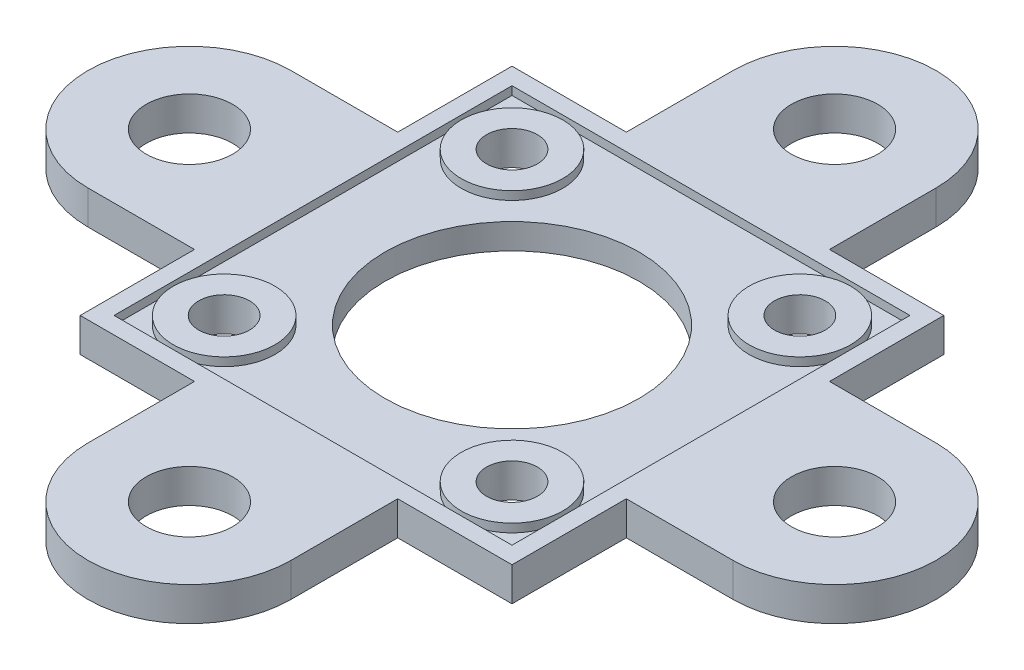
SolidWorks part; units mm, degrees
ref_plane "Front Plane" through (0, 0, 0) normal (0, 0, 1) x (1, 0, 0)
ref_plane "Top Plane" through (0, 0, 0) normal (0, 1, 0) x (1, 0, 0)
ref_plane "Right Plane" through (0, 0, 0) normal (1, 0, 0) x (0, 0, -1)
other "Bounding Box"
ref_plane "Default Plane" through (-8.9266, -12.7485, 0) normal (-0.1736, 0.9848, 0) x (0.9848, 0.1736, 0)
sketch "Sketch1" plane through (0, 0, 0) normal (0, 1, 0) x (1, 0, 0)
  line L1 (-11.5, -11.5) -> (11.5, -11.5)
  line L2 (-11.5, -11.5) -> (-11.5, 11.5)
  line L3 (-11.5, 11.5) -> (11.5, 11.5)
  line L4 (11.5, -11.5) -> (11.5, 11.5)
  line L5 (-11.5, -11.5) -> (11.5, 11.5) construction
  line L6 (-11.5, 11.5) -> (11.5, -11.5) construction
  line L7 (-8.5, 8.5) -> (8.5, 8.5) construction
  line L8 (-8.5, 8.5) -> (-8.5, -8.5) construction
  line L9 (-8.5, -8.5) -> (8.5, -8.5) construction
  line L10 (8.5, 8.5) -> (8.5, -8.5) construction
  line L11 (-8.5, 8.5) -> (8.5, -8.5) construction
  line L12 (-8.5, -8.5) -> (8.5, 8.5) construction
  circle A0 centre (-8.5, 8.5) radius 1.5
  circle A1 centre (8.5, 8.5) radius 1.5
  circle A2 centre (8.5, -8.5) radius 1.5
  circle A3 centre (-8.5, -8.5) radius 1.5
  point P0 (0, 0)
  point P6 (0, 0)
  dimension "D3" = 3
  dimension "D1" = 17
  dimension "D2" = 23
extrude "Boss-Extrude1" add sketch "Sketch1" along normal blind 1
sketch "Sketch2" plane through (0, 1, 0) normal (0, 1, 0) x (1, 0, 0)
  line L1 (-3, 2.5) -> (3, 2.5)
  line L2 (-3, 2.5) -> (-3, -2.5)
  line L3 (-3, -2.5) -> (3, -2.5)
  line L4 (3, 2.5) -> (3, -2.5)
  line L5 (-3, 2.5) -> (3, -2.5) construction
  line L6 (-3, -2.5) -> (3, 2.5) construction
  point P0 (0, 0)
  dimension "D1" = 5
  dimension "D2" = 6
extrude "Boss-Extrude2" add sketch "Sketch2" along normal blind 1
fillet "Fillet1" radius 3 4 edges at (-11.5, 0.5, -11.5) (11.5, 0.5, -11.5) (11.5, 0.5, 11.5) (-11.5, 0.5, 11.5)
sketch "Sketch3" plane through (0, 1, 0) normal (0, 1, 0) x (1, 0, 0)
  line L0 (-11.5, 8.5) -> (-11.5, -8.5) construction
  line L1 (-11.75, 11.75) -> (11.75, 11.75) construction
  line L2 (-11.75, 11.75) -> (-11.75, -11.75) construction
  line L3 (-11.75, -11.75) -> (11.75, -11.75) construction
  line L4 (11.75, 11.75) -> (11.75, -11.75) construction
  line L5 (-11.75, 11.75) -> (11.75, -11.75) construction
  line L6 (-11.75, -11.75) -> (11.75, 11.75) construction
  line L8 (-12.75, 12.75) -> (12.75, 12.75)
  line L9 (-12.75, 12.75) -> (-12.75, -12.75)
  line L10 (-12.75, -12.75) -> (12.75, -12.75)
  line L11 (12.75, 12.75) -> (12.75, -12.75)
  line L12 (-12.75, 12.75) -> (12.75, -12.75) construction
  line L13 (-12.75, -12.75) -> (12.75, 12.75) construction
  circle A0 centre (-8.5, 8.5) radius 1.5 construction
  circle A1 centre (8.5, 8.5) radius 1.5 construction
  circle A2 centre (8.5, -8.5) radius 1.5 construction
  circle A3 centre (-8.5, -8.5) radius 1.5 construction
  circle A4 centre (-8.5, 8.5) radius 1.5
  circle A5 centre (8.5, 8.5) radius 1.5
  circle A6 centre (8.5, -8.5) radius 1.5
  circle A7 centre (-8.5, -8.5) radius 1.5
  circle A8 centre (0, 0) radius 7.5
  point P12 (0, 0)
  point P20 (0, 0)
  dimension "D3" = 15
  dimension "D1" = 0.25
  dimension "D2" = 1
extrude "Boss-Extrude3" add sketch "Sketch3" along normal blind 1.5 from offset 3 separate body offset against normal yes
sketch "Sketch4" plane through (0, -2, 0) normal (0, -1, 0) x (1, 0, 0)
  circle A0 centre (-8.5, 8.5) radius 3
  circle A1 centre (-8.5, -8.5) radius 1.5
  circle A2 centre (-8.5, -8.5) radius 1.5
  circle A3 centre (8.5, -8.5) radius 1.5
  circle A4 centre (8.5, -8.5) radius 1.5
  circle A5 centre (8.5, 8.5) radius 1.5
  circle A6 centre (8.5, 8.5) radius 1.5
  circle A7 centre (-8.5, 8.5) radius 1.5
  circle A8 centre (-8.5, 8.5) radius 1.5
  circle A9 centre (8.5, 8.5) radius 3
  circle A10 centre (8.5, -8.5) radius 3
  circle A11 centre (-8.5, -8.5) radius 3
  arc A12 (-8.5, 11.5) -> (-11.5, 8.5) centre (-8.5, 8.5) ccw construction
  dimension "D1" = 0
  dimension "D2" = 0
  dimension "D3" = 0
  dimension "D4" = 0
extrude "Boss-Extrude4" add sketch "Sketch4" against normal up to surface (2 mm away) up to face at (8.5, 0, 10)
sketch "Sketch5" plane through (0, -2, 0) normal (0, -1, 0) x (1, 0, 0)
  line L0 (11.75, -11.75) -> (11.75, 11.75) construction
  line L1 (-11.75, 11.75) -> (11.75, 11.75) construction
  line L2 (-11.75, -11.75) -> (-11.75, 11.75) construction
  line L3 (-11.75, -11.75) -> (11.75, -11.75) construction
  line L4 (-12.75, -12.75) -> (12.75, -12.75) construction
  line L5 (12.75, -12.75) -> (12.75, 12.75) construction
  line L6 (-12.75, 12.75) -> (12.75, 12.75) construction
  line L7 (-12.75, -12.75) -> (-12.75, 12.75) construction
  line L8 (11.75, -11.75) -> (11.75, 11.75)
  line L9 (-11.75, 11.75) -> (11.75, 11.75)
  line L10 (-11.75, -11.75) -> (-11.75, 11.75)
  line L11 (-11.75, -11.75) -> (11.75, -11.75)
  line L12 (-12.75, -12.75) -> (12.75, -12.75)
  line L13 (12.75, -12.75) -> (12.75, 12.75)
  line L14 (-12.75, 12.75) -> (12.75, 12.75)
  line L15 (-12.75, -12.75) -> (-12.75, 12.75)
extrude "Boss-Extrude5" add sketch "Sketch5" against normal blind 2
sketch "Sketch6" plane through (0, 0, 0) normal (0, 1, 0) x (-1, 0, 0)
  line L0 (0, -19.05) -> (0, 0) construction
  line L1 (-6, -19.05) -> (-6, -12.75)
  line L2 (12.75, -12.75) -> (-12.75, -12.75) construction
  line L3 (-6, -12.75) -> (6, -12.75)
  line L4 (6, -12.75) -> (6, -19.05)
  circle A0 centre (0, -19.05) radius 2.5527
  arc A1 (-6, -19.05) -> (6, -19.05) centre (0, -19.05) ccw
  dimension "D2" = 5.1054
  dimension "D3" = 6
  dimension "D1" = 19.05
extrude "Boss-Extrude6" add sketch "Sketch6" against normal blind 2
ref_axis "Axis1" through (0, -0.175, 0) along (0, 1, 0)
pattern_circular "CirPattern1" count 4 over 360 about axis through (0, -0.175, 0) along (0, 1, 0) of "Boss-Extrude6"
delete or keep bodies "Body-Delete/Keep 1" type keep bodies bodies 110
